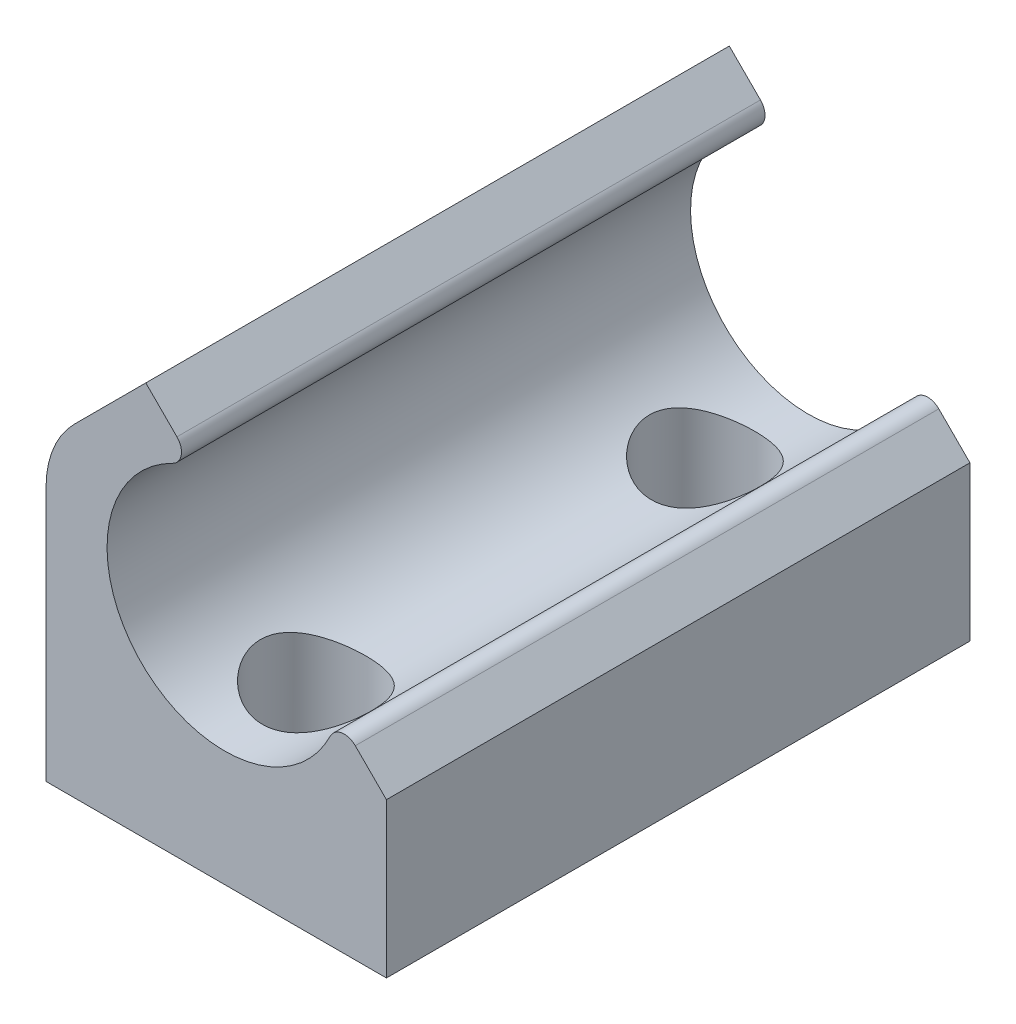
SolidWorks part; units mm, degrees
ref_plane "Front Plane" through (0, 0, 0) normal (0, 0, 1) x (1, 0, 0)
ref_plane "Top Plane" through (0, 0, 0) normal (0, 1, 0) x (1, 0, 0)
ref_plane "Right Plane" through (0, 0, 0) normal (1, 0, 0) x (0, 0, -1)
sketch "Sketch1" plane through (0, 0, 0) normal (0, 0, 1) x (1, 0, 0)
  line L0 (0, 0) -> (17.5, 0)
  line L1 (17.5, 0) -> (17.5, 7.94)
  line L2 (17.5, 7.94) -> (15.0251, 10.4149)
  line L3 (7.6032, 17.8368) -> (5.1283, 20.3117)
  line L4 (5.1283, 20.3117) -> (0, 15.1833)
  line L5 (0, 15.1833) -> (0, 0)
  arc A0 (15.0251, 10.4149) -> (7.6032, 17.8368) centre (9.1858, 11.9974) cw
  dimension "D1" = 6.05
  dimension "D2" = 3.5
  dimension "D3" = 17.5
  dimension "D4" = 7.94
  dimension "D5" = 3.01
  dimension "D6" = 45
extrude "Boss-Extrude1" add sketch "Sketch1" along normal blind 30
fillet "Fillet1" radius 0.8 2 edges at (15.0251, 10.4149, 15) (7.6032, 17.8368, 15)
ref_plane "Plane1" through (0, 9.3284, 0) normal (0, -1, 0) x (-1, 0, 0)
sketch "Sketch3" plane through (0, 9.3284, 0) normal (0, -1, 0) x (-1, 0, 0)
  line L0 (-3.1358, 0) -> (-14.6152, 0) construction
  line L1 (-3.1358, 0) -> (-14.6152, 0) construction
  circle A0 centre (-8.8755, -5) radius 2.85
  circle A1 centre (-8.8755, -25) radius 2.85
  point P7 (-8.8755, 0)
  dimension "D1" = 5.7
  dimension "D2" = 5
  dimension "D3" = 20
extrude "Cut-Extrude1" cut sketch "Sketch3" along normal blind 9
sketch "Sketch4" plane through (0, 9.3284, 0) normal (0, -1, 0) x (-1, 0, 0)
  circle A0 centre (-8.8755, -5) radius 1.55
  circle A1 centre (-8.8755, -25) radius 1.55
  dimension "D1" = 3.1
  dimension "D2" = 3.1
extrude "Cut-Extrude2" cut sketch "Sketch4" along normal through all
fillet "Fillet2" radius 5 1 edges at (0, 15.1833, 15)
